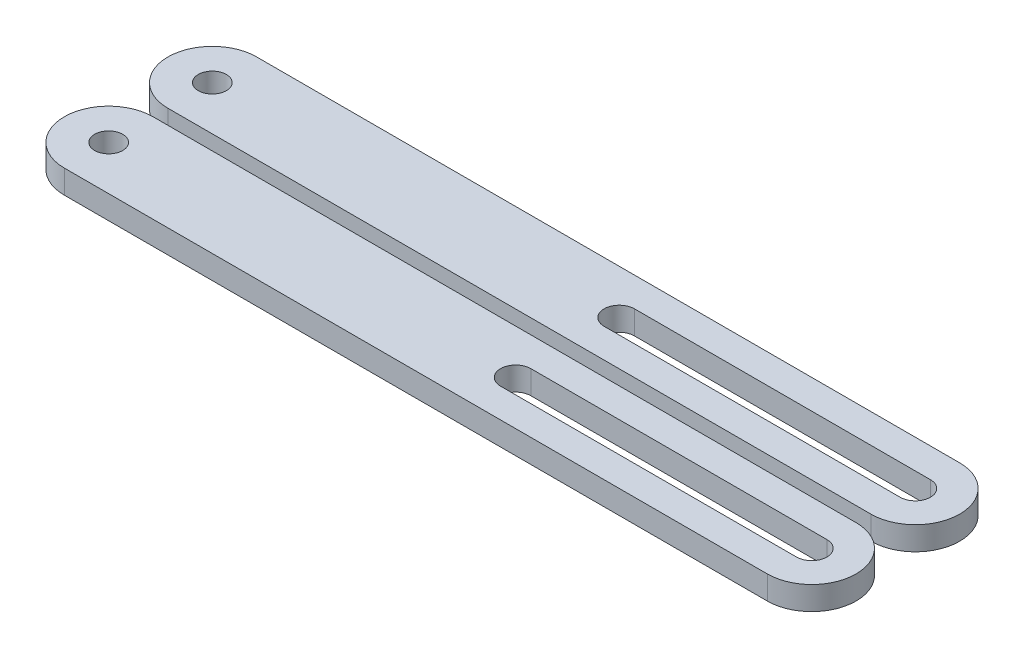
SolidWorks part; units mm, degrees
ref_plane "Front Plane" through (0, 0, 0) normal (0, 0, 1) x (1, 0, 0)
ref_plane "Top Plane" through (0, 0, 0) normal (0, 1, 0) x (1, 0, 0)
ref_plane "Right Plane" through (0, 0, 0) normal (1, 0, 0) x (0, 0, -1)
sketch "Sketch1" plane through (0, 0, 0) normal (0, 1, 0) x (1, 0, 0)
  line L0 (0, 0) -> (100, 0) construction
  line L4 (55, 0) -> (95, 0) construction
  line L5 (55, 2.05) -> (95, 2.05)
  line L6 (55, -2.05) -> (95, -2.05)
  line L7 (0, 0) -> (95, 0) construction
  line L8 (0, 6) -> (95, 6)
  line L9 (0, -6) -> (95, -6)
  circle A1 centre (0, 0) radius 1.9
  arc A2 (0, -6) -> (0, 6) centre (0, 0) ccw construction
  arc A3 (55, 2.05) -> (55, -2.05) centre (55, 0) ccw
  arc A4 (95, -2.05) -> (95, 2.05) centre (95, 0) ccw
  circle A5 centre (0, 0) radius 11.725 construction
  arc A8 (0, 6) -> (0, -6) centre (0, 0) ccw
  arc A9 (95, -6) -> (95, 6) centre (95, 0) ccw
  point P11 (75, 0)
  point P17 (47.5, 0)
  dimension "D1" = 3.8
  dimension "D2" = 12
  dimension "D5" = 4.1
  dimension "D9" = 23.45
  dimension "D4" = 100
  dimension "D6" = 40
  dimension "D7" = 5
extrude "Boss-Extrude1" add sketch "Sketch1" along normal blind 3.175
sketch "Sketch2" plane through (0, 0, 0) normal (0, 1, 0) x (1, 0, 0)
  line L0 (0, 16.069) -> (0, 0)
  line L1 (0, 0) -> (63.4626, 0)
pattern_linear "LPattern1" count 2 spacing 14 along (0, 0, -1) of bodies 101
